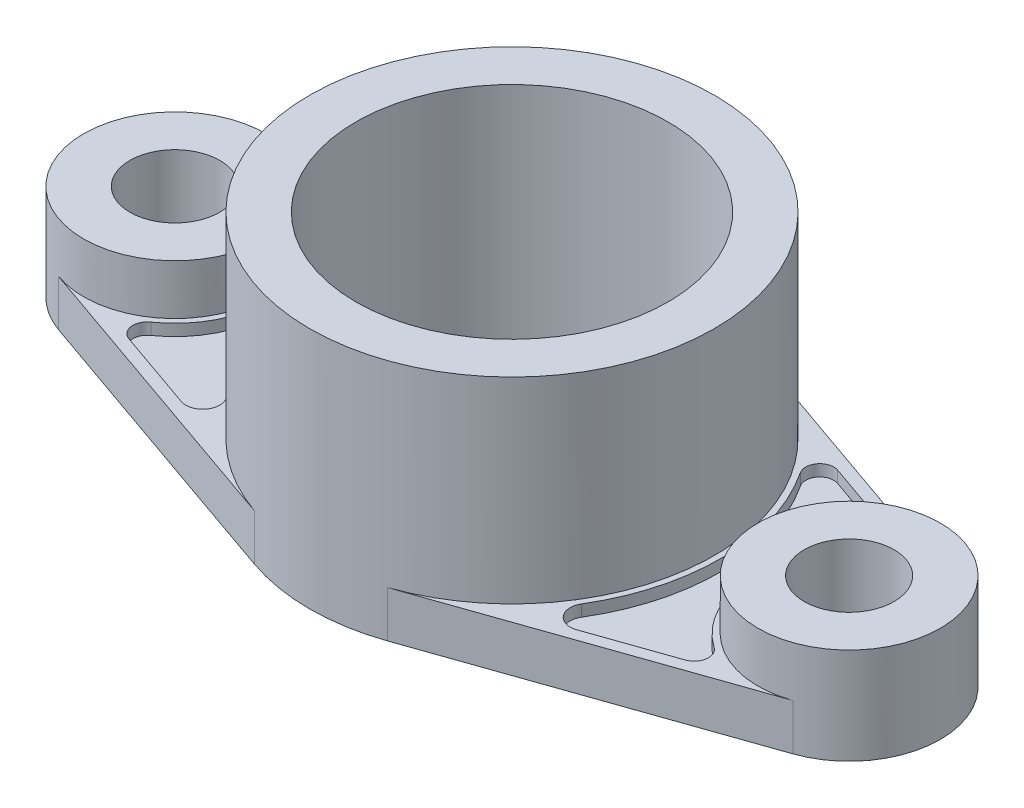
SolidWorks part; units mm, degrees
ref_plane "Front Plane" through (0, 0, 0) normal (0, 0, 1) x (1, 0, 0)
ref_plane "Top Plane" through (0, 0, 0) normal (0, 1, 0) x (1, 0, 0)
ref_plane "Right Plane" through (0, 0, 0) normal (1, 0, 0) x (0, 0, -1)
sketch "Sketch1" plane through (0, 0, 0) normal (0, 1, 0) x (1, 0, 0)
  line L0 (-126.1535, 0) -> (84.9756, 0) construction
  line L1 (0, 51.918) -> (0, -58.5502) construction
  line L2 (-17.301, 49.5674) -> (-95.2986, 22.3431)
  line L3 (-17.301, -49.5674) -> (-95.2986, -22.3431)
  line L4 (-49.2924, 35.2236) -> (-73.0616, 26.9272)
  line L5 (-72.1968, -27.2291) -> (-51.3207, -34.5156)
  line L6 (72.1968, -27.2291) -> (51.3207, -34.5156)
  line L7 (49.2924, 35.2236) -> (73.0616, 26.9272)
  line L8 (17.301, -49.5674) -> (95.2986, -22.3431)
  line L9 (17.301, 49.5674) -> (95.2986, 22.3431)
  circle A0 centre (0, 0) radius 52.5
  circle A1 centre (0, 0) radius 40.5
  circle A2 centre (-87.5, 0) radius 11.665
  circle A3 centre (-87.5, 0) radius 23.665
  arc A4 (-45.0507, 29.773) -> (-46.1221, -28.0847) centre (0, 0) ccw
  arc A5 (-73.1027, -20.6397) -> (-73.7694, 21.0891) centre (-87.5, 0) ccw
  arc A6 (-73.0616, 26.9272) -> (-73.7694, 21.0891) centre (-71.982, 23.8343) ccw
  arc A7 (-49.2924, 35.2236) -> (-45.0507, 29.773) centre (-48.0914, 31.7825) cw
  arc A8 (-72.1968, -27.2291) -> (-73.1027, -20.6397) centre (-70.966, -23.7029) cw
  arc A9 (-51.3207, -34.5156) -> (-46.1221, -28.0847) centre (-49.8734, -30.369) ccw
  arc A10 (51.3207, -34.5156) -> (46.1221, -28.0847) centre (49.8734, -30.369) cw
  arc A11 (72.1968, -27.2291) -> (73.1027, -20.6397) centre (70.966, -23.7029) ccw
  arc A12 (49.2924, 35.2236) -> (45.0507, 29.773) centre (48.0914, 31.7825) ccw
  arc A13 (73.0616, 26.9272) -> (73.7694, 21.0891) centre (71.982, 23.8343) cw
  arc A14 (73.1027, -20.6397) -> (73.7694, 21.0891) centre (87.5, 0) cw
  arc A15 (45.0507, 29.773) -> (46.1221, -28.0847) centre (0, 0) cw
  circle A16 centre (87.5, 0) radius 23.665
  circle A17 centre (87.5, 0) radius 11.665
  point P46 (-126.1535, 0)
  dimension "D1" = 81
  dimension "D2" = 105
  dimension "D3" = 47.33
  dimension "D4" = 50.33
  dimension "D6" = 108
  dimension "D5" = 87.5
  dimension "D7" = 3
  dimension "D8" = 3
extrude "Boss-Extrude1" add sketch "Sketch1" along normal blind 12 contours L8 A16 L9 A0 A15 A12 L7 A13 A14 A11 L6 A10 | A3 L3 A0 L2 A9 L5 A8 A5 A6 L4 A7 A4 region at (-53.7614, 0, 0) region at (55.8841, 0, -34.7643)
extrude "Boss-Extrude2" add sketch "Sketch1<3>" along normal blind 9 contours A12 A15 A10 L6 A11 A14 A13 L7 | L5 A9 A4 A7 L4 A6 A5 A8 region at (-58.99, 0, -0.3552) region at (58.99, 0, -0.3552)
sketch "Sketch1<3>" plane through (0, 0, 0) normal (0, 1, 0) x (1, 0, 0) same geometry as "Sketch1"
extrude "Boss-Extrude3" add sketch "Sketch1<4>" along normal blind 63 contours A0 A1 region at (0, 0, -51.0151)
sketch "Sketch1<4>" plane through (0, 0, 0) normal (0, 1, 0) x (1, 0, 0) same geometry as "Sketch1"
extrude "Boss-Extrude4" add sketch "Sketch1<5>" along normal blind 25 contours A3 A2 | A16 A17 region at (-74.1858, 0, -18.7492) region at (106.2492, 0, -13.3142)
sketch "Sketch1<5>" plane through (0, 0, 0) normal (0, 1, 0) x (1, 0, 0) same geometry as "Sketch1"
